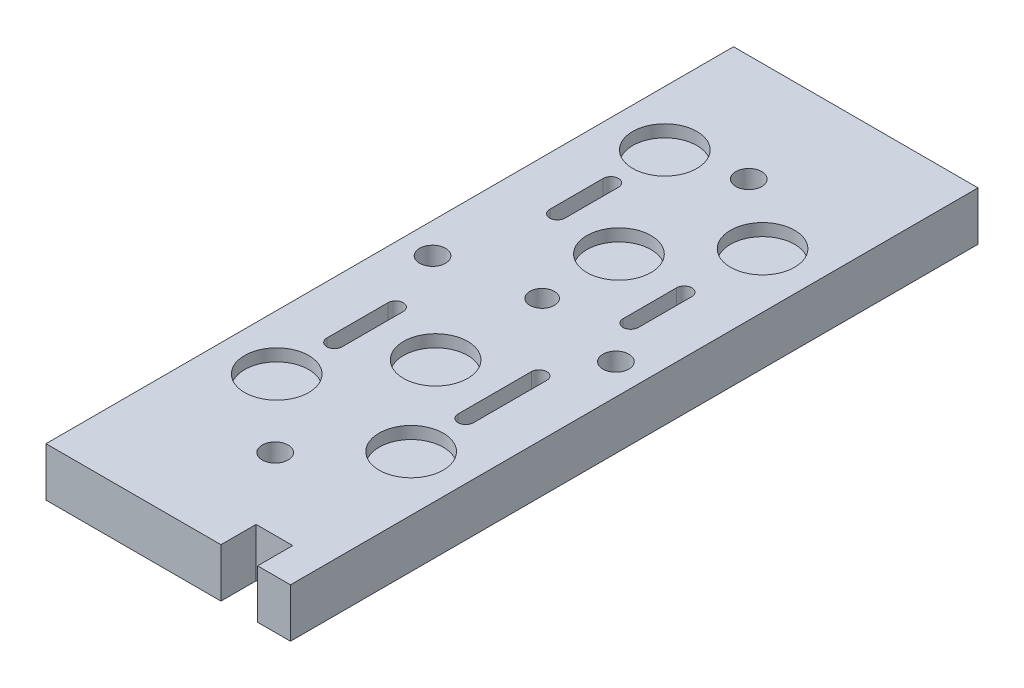
SolidWorks part; units mm, degrees
material "Plain Carbon Steel"
ref_plane "Front Plane" through (0, 0, 0) normal (0, 0, 1) x (1, 0, 0)
ref_plane "Top Plane" through (0, 0, 0) normal (0, 1, 0) x (1, 0, 0)
ref_plane "Right Plane" through (0, 0, 0) normal (1, 0, 0) x (0, 0, -1)
sketch "Sketch1" plane through (0, 0, 0) normal (0, 1, 0) x (1, 0, 0)
  line L1 (-40, -112.5) -> (40, -112.5)
  line L2 (-40, -112.5) -> (-40, 112.5)
  line L3 (-40, 112.5) -> (40, 112.5)
  line L4 (40, -112.5) -> (40, 112.5)
  line L5 (-40, -112.5) -> (40, 112.5) construction
  line L6 (-40, 112.5) -> (40, -112.5) construction
  point P0 (0, 0)
  dimension "D1" = 225
  dimension "D2" = 80
extrude "Boss-Extrude1" add sketch "Sketch1" against normal blind 16
sketch "Sketch2" plane through (0, 0, 0) normal (0, 1, 0) x (1, 0, 0)
  line L0 (-19, 36.36) -> (-19, 53.86) construction
  line L1 (-24, 53.86) -> (-24, 36.36) construction
  line L2 (-19, -36.59) -> (-19, -16.59) construction
  line L3 (-24, -16.59) -> (-24, -36.59) construction
  line L4 (24, 17.36) -> (24, 34.86) construction
  line L5 (19, 34.86) -> (19, 17.36) construction
  line L8 (24, -36.64) -> (24, -12.64) construction
  line L9 (19, -12.64) -> (19, -36.64) construction
  line L11 (-19, 36.36) -> (-19, 53.86)
  line L14 (-24, 53.86) -> (-24, 36.36)
  line L15 (-19, -36.59) -> (-19, -16.59)
  line L16 (-24, -16.59) -> (-24, -36.59)
  line L17 (24, 17.36) -> (24, 34.86)
  line L20 (19, 34.86) -> (19, 17.36)
  line L21 (24, -36.64) -> (24, -12.64)
  line L23 (19, -12.64) -> (19, -36.64)
  arc A0 (-24, 36.36) -> (-19, 36.36) centre (-21.5, 36.36) ccw construction
  arc A1 (-19, 53.86) -> (-24, 53.86) centre (-21.5, 53.86) ccw construction
  arc A2 (-24, -36.59) -> (-19, -36.59) centre (-21.5, -36.59) ccw construction
  arc A3 (-19, -16.59) -> (-24, -16.59) centre (-21.5, -16.59) ccw construction
  arc A4 (19, 17.36) -> (24, 17.36) centre (21.5, 17.36) ccw construction
  arc A5 (24, 34.86) -> (19, 34.86) centre (21.5, 34.86) ccw construction
  arc A8 (19, -36.64) -> (24, -36.64) centre (21.5, -36.64) ccw construction
  arc A9 (24, -12.64) -> (19, -12.64) centre (21.5, -12.64) ccw construction
  arc A14 (-24, 36.36) -> (-19, 36.36) centre (-21.5, 36.36) ccw
  arc A15 (-19, 53.86) -> (-24, 53.86) centre (-21.5, 53.86) ccw
  arc A16 (-24, -36.59) -> (-19, -36.59) centre (-21.5, -36.59) ccw
  arc A17 (-19, -16.59) -> (-24, -16.59) centre (-21.5, -16.59) ccw
  arc A20 (19, 17.36) -> (24, 17.36) centre (21.5, 17.36) ccw
  arc A21 (24, 34.86) -> (19, 34.86) centre (21.5, 34.86) ccw
  arc A26 (19, -36.64) -> (24, -36.64) centre (21.5, -36.64) ccw
  arc A27 (24, -12.64) -> (19, -12.64) centre (21.5, -12.64) ccw
extrude "Cut-Extrude1" cut sketch "Sketch2" against normal up to next
sketch "Sketch4" plane through (0, 0, 0) normal (0, 1, 0) x (1, 0, 0)
  circle A0 centre (-22, 72) radius 10.5
  circle A1 centre (22, 60) radius 10.5
  circle A2 centre (0, 35) radius 10.5
  circle A3 centre (0, -25) radius 10.5
  circle A4 centre (22, -55) radius 10.5
  circle A5 centre (-22, -55) radius 10.5
extrude "Cut-Extrude2" cut sketch "Sketch4" against normal blind 4
sketch "Sketch5" plane through (0, -16, 0) normal (0, -1, 0) x (1, 0, 0)
  circle A0 centre (0, 100) radius 8.5
  circle A1 centre (0, -100) radius 8.5
  dimension "D1" = 17
extrude "Cut-Extrude3" cut sketch "Sketch5" against normal blind 5
sketch "Sketch6" plane through (0, 0, 0) normal (0, 1, 0) x (1, 0, 0)
  line L0 (-40, -112.5) -> (40, -112.5) construction
  line L1 (17.25, -112.5) -> (29.25, -112.5)
  line L2 (17.25, -112.5) -> (17.25, -101)
  line L3 (17.25, -101) -> (29.25, -101)
  line L4 (29.25, -112.5) -> (29.25, -101)
  line L5 (28.25, -102.5) -> (28.25, -115) construction
  line L6 (18.25, -115) -> (18.25, -102.5) construction
  line L7 (18.75, -102) -> (27.75, -102) construction
  point P8 (28.25, -108.75)
  point P11 (18.25, -108.75)
  dimension "D1" = 1
  dimension "D2" = 1
  dimension "D3" = 1
extrude "Cut-Extrude4" cut sketch "Sketch6" against normal up to next
hole_wizard "M10 Tapped Hole1" positions "Sketch9" profile "Sketch8" tap size "M10" standard "ISO" end condition through all
sketch "Sketch9" plane through (0, 0, 0) normal (0, 1, 0) x (1, 0, 0)
  point P0 (0, -77.5)
  point P2 (30, 4)
  point P4 (-30, 4)
  point P6 (0, 77.5)
  dimension "D1" = 77.5
  dimension "D2" = 77.5
  dimension "D3" = 4
  dimension "D4" = 30
  dimension "D5" = 30
sketch "Sketch8" plane through (0, 0, 77.5) normal (1, 0, 0) x (0, 0, 1)
  line L0 (0, 0) -> (0, 16)
  line L1 (0, 16) -> (4.25, 16)
  line L2 (4.25, 16) -> (4.25, 0)
  line L5 (4.25, 0) -> (0, 0)
  line L11 (0, -6.35) -> (0, 107.95) construction
  dimension "Thru Tap Drill Dia." = 8.5
  dimension "Thru Tap Drill Depth" = 16
cosmetic thread "Hole Thread1" parameters "D2"=10
cosmetic thread "Hole Thread2" parameters "D2"=10
cosmetic thread "Hole Thread3" parameters "D2"=10
cosmetic thread "Hole Thread4" parameters "D2"=10
sketch "Sketch10" plane through (0, 0, 0) normal (0, 1, 0) x (1, 0, 0)
  circle A0 centre (0, 9.86) radius 5 construction
  circle A1 centre (0, 9.86) radius 5 construction
  circle A2 centre (0, 9.86) radius 4
  dimension "D1" = 8
extrude "Cut-Extrude5" cut sketch "Sketch10" against normal up to next
